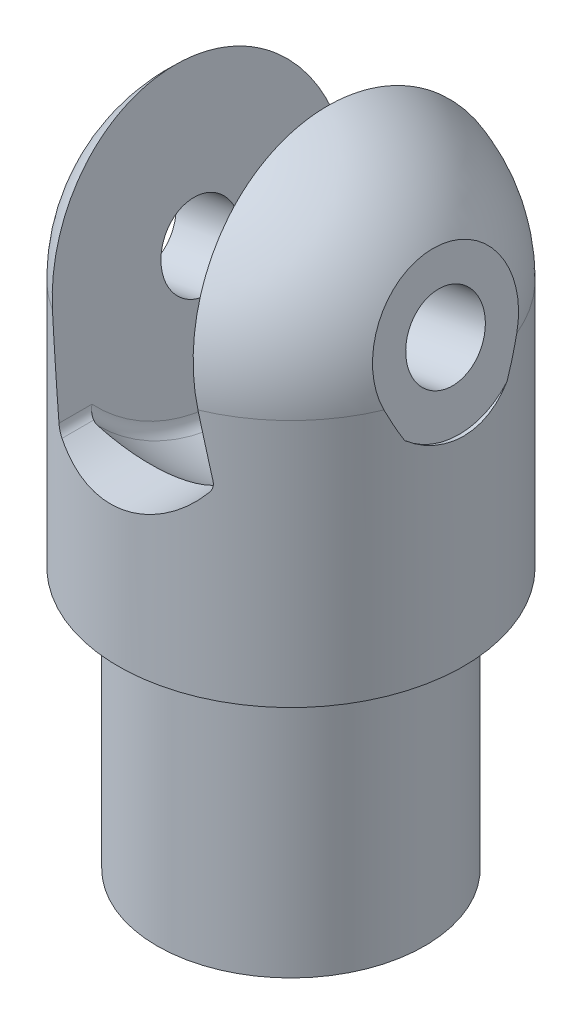
SolidWorks part; units mm, degrees
ref_plane "Front Plane" through (0, 0, 0) normal (0, 0, 1) x (1, 0, 0)
ref_plane "Top Plane" through (0, 0, 0) normal (0, 1, 0) x (1, 0, 0)
ref_plane "Right Plane" through (0, 0, 0) normal (1, 0, 0) x (0, 0, -1)
sketch "Sketch1" plane through (0, 0, 0) normal (0, 1, 0) x (1, 0, 0)
  circle A0 centre (0, 0) radius 12.9921
extrude "Boss-Extrude1" add sketch "Sketch1" along normal blind 25.4 contours A0
sketch "Sketch2" plane through (0, 0, 0) normal (1, 0, 0) x (0, 0, -1)
  line L0 (-16.764, 25.4) -> (-16.764, 49.53)
  line L1 (0, 25.4) -> (-16.764, 25.4)
  line L4 (12.9921, 25.4) -> (-12.9921, 25.4) construction
  line L5 (0, 14.2913) -> (0, -14.2913) construction
  line L6 (0, 25.4) -> (0, 66.294)
  arc A0 (0, 66.294) -> (-16.764, 49.53) centre (0, 49.53) ccw
  dimension "D1" = 33.528
  dimension "D2" = 24.13
revolve "Revolve1" add sketch "Sketch2" angle 360 about L6
ref_plane "Plane2" through (0, 49.53, 0) normal (0, -1, 0) x (-1, 0, 0)
ref_axis "Axis1" through (0, 49.53, 23.7) along (0, 0, -1)
ref_plane "Plane3" through (-8.4701, 48.0365, 0) normal (0.1736, -0.9848, 0) x (0, 0, -1)
ref_plane "Plane4" through (8.4701, 1.4935, 0) normal (-0.9848, -0.1736, 0) x (0, 0, -1)
sketch "Sketch3" plane through (-8.6008, 98.3075, 0) normal (-0.9848, -0.1736, 0) x (0, 0, -1)
  line L1 (-23.7, 49.53) -> (13.1808, 49.53) construction
  line L2 (0, 49.53) -> (0, 73.2934) construction
  circle A2 centre (0, 49.53) radius 3.81
  point P2 (-1.4065, 49.53)
  point P8 (0.3682, 49.1662)
  point P9 (0, 0)
  dimension "D1" = 7.62
extrude "Cut-Extrude1" cut sketch "Sketch3" against normal through all both and the other way through all
ref_axis "Axis2" through (17.3849, 52.5954, 0) along (-0.9848, -0.1736, 0)
sketch "Sketch10" plane through (0, 0, 0) normal (0, 0, 1) x (1, 0, 0)
  line L0 (17.3849, 52.5954) -> (-17.4651, 46.4504) construction
  line L1 (-8.7549, 47.9863) -> (6.2535, 50.6327)
  point P4 (7.3613, 50.828)
  point P5 (-1.2507, 49.3095)
  dimension "D1" = 15.24
  dimension "D2" = 1.27
sketch "Sketch11" plane through (0, 0, 0) normal (0, 0, 1) x (1, 0, 0)
  line L2 (-8.7549, 47.9863) -> (6.2535, 50.6327) construction
  line L3 (-8.7549, 47.9863) -> (-11.5554, 63.8683)
  line L4 (6.2535, 50.6327) -> (3.2519, 67.6556)
  line L5 (-8.7549, 47.9863) -> (6.2535, 50.6327)
  arc A0 (3.2519, 67.6556) -> (-11.5554, 63.8683) centre (0, 49.53) ccw
  arc A1 (15.4157, 56.117) -> (-16.7389, 50.4473) centre (0, 49.53) ccw construction
  point P1 (7.5042, 50.8532)
  point P12 (7.5042, 50.8532)
  point P15 (7.5042, 50.8532)
  dimension "D1" = 18.415
revolve "Cut-Revolve10" cut sketch "Sketch11" angle 180 about axis through (17.3849, 52.5954, 0) along (-0.9848, -0.1736, 0) other way angle 90
sketch "Sketch13" plane through (0, 0, 0) normal (0, 0, 1) x (1, 0, 0)
  line L0 (-9.4165, 51.7384) -> (5.5919, 54.3848)
  line L1 (-9.0271, 49.53) -> (-11.2229, 61.983) construction
  line L2 (3.5594, 65.9118) -> (6.448, 49.53) construction
  line L3 (-8.7549, 47.9863) -> (6.2535, 50.6327) construction
  line L4 (-9.4165, 51.7384) -> (-12.3277, 68.2482)
  line L5 (5.5919, 54.3848) -> (2.6808, 70.8946)
  arc A0 (2.6808, 70.8946) -> (-12.3277, 68.2482) centre (-1.9123, 53.0616) ccw
  dimension "D1" = 3.81
  dimension "D2" = 36.83
revolve "Cut-Revolve11" cut sketch "Sketch13" angle 360 about L0
sketch "Sketch14" plane through (0, 0, 0) normal (0, 0, 1) x (1, 0, 0)
  line L0 (-8.7549, 47.9863) -> (6.2535, 50.6327) construction
  line L1 (-8.7549, 47.9863) -> (-7.4585, 40.6336)
  line L2 (6.2535, 50.6327) -> (7.55, 43.28)
  line L3 (-8.7549, 47.9863) -> (6.2535, 50.6327)
  arc A0 (-7.4585, 40.6336) -> (7.55, 43.28) centre (-1.2507, 49.3095) ccw
  dimension "D1" = 21.336
extrude "Cut-Extrude4" cut sketch "Sketch14" along normal blind 32.004
fillet "Fillet1" radius 1.27 8 edges at (-6.4265, 34.781, -8.9599) (-6.23, 33.6664, 0) (-6.7543, 36.6402, 6.7827) (-7.4585, 40.6336, 13.7095) (7.55, 43.28, 13.6866) (8.2541, 39.2866, 6.7827) (8.8791, 35.7424, 0) (8.8638, 35.8292, -8.5343)
ref_plane "Plane5" through (-6.5383, -1.1529, 0) normal (-0.9848, -0.1736, 0) x (0, 0, -1)
sketch "Sketch15" plane through (-6.5383, -1.1529, 0) normal (-0.9848, -0.1736, 0) x (0, 0, -1)
  circle A0 centre (0, -48.7775) radius 7.62
  dimension "D1" = 15.24
extrude "Cut-Extrude5" cut sketch "Sketch15" along normal blind 10.16
mirror "Mirror1" about plane through (8.4701, 1.4935, 0) normal (-0.9848, -0.1736, 0) of "Cut-Extrude5"
